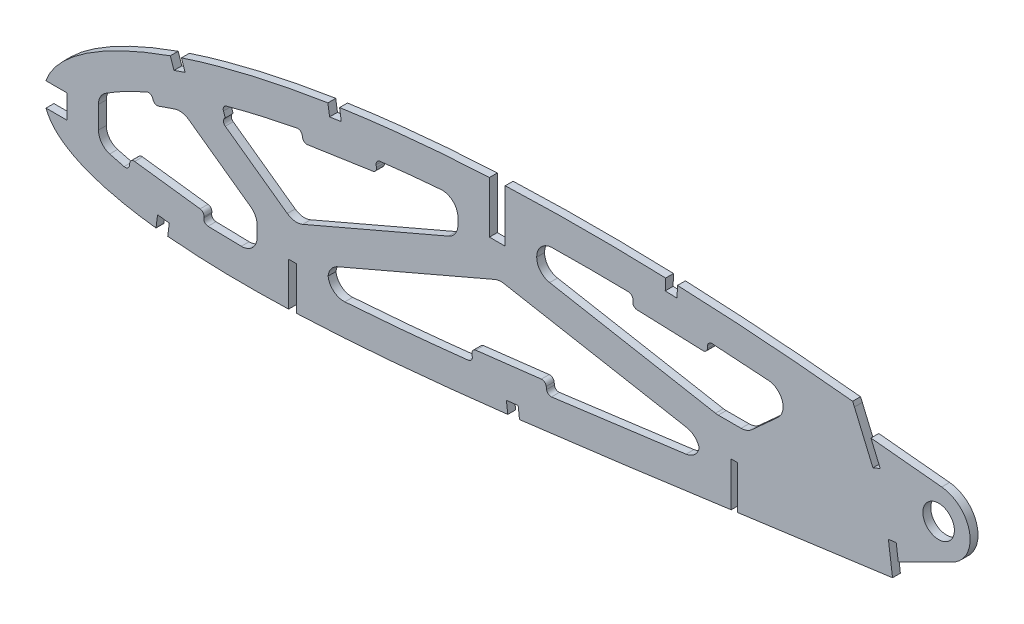
SolidWorks part; units mm, degrees
material "Pine"
ref_plane "Front Plane" through (0, 0, 0) normal (0, 0, 1) x (1, 0, 0)
ref_plane "Top Plane" through (0, 0, 0) normal (0, 1, 0) x (1, 0, 0)
ref_plane "Right Plane" through (0, 0, 0) normal (1, 0, 0) x (0, 0, -1)
curve "Curve2"
  spline degree 3 poles (520.229, 0.8111, 0) (520.1892, 0.8357, 0) (520.0299, 0.9341, 0) (519.6711, 1.1542, 0) (519.0735, 1.5208, 0) (518.237, 2.0313, 0) (517.1622, 2.6844, 0) (515.8486, 3.4756, 0) (514.2969, 4.4021, 0) (512.5075, 5.4598, 0) (510.4807, 6.6436, 0) (508.2172, 7.9486, 0) (505.7172, 9.3676, 0) (502.9816, 10.8948, 0) (500.0114, 12.5227, 0) (496.8072, 14.2443, 0) (493.3701, 16.0505, 0) (489.7015, 17.9338, 0) (485.8019, 19.8836, 0) (481.6733, 21.8919, 0) (477.317, 23.9487, 0) (472.7345, 26.0429, 0) (467.9284, 28.1661, 0) (462.9001, 30.305, 0) (457.6524, 32.4505, 0) (452.1876, 34.5902, 0) (446.5089, 36.7144, 0) (440.6184, 38.8094, 0) (434.5207, 40.866, 0) (428.2186, 42.8708, 0) (421.7166, 44.813, 0) (415.0186, 46.68, 0) (408.1302, 48.4622, 0) (401.0555, 50.1466, 0) (393.8008, 51.7219, 0) (386.3718, 53.1787, 0) (378.7746, 54.5024, 0) (371.0303, 55.692, 0) (363.2636, 56.6815, 0) (355.5128, 57.652, 0) (347.7736, 58.5637, 0) (339.9398, 59.4368, 0) (332.019, 60.2663, 0) (324.019, 61.0497, 0) (315.9478, 61.7836, 0) (307.814, 62.4658, 0) (299.6253, 63.0925, 0) (291.3904, 63.6628, 0) (283.1174, 64.1714, 0) (274.8152, 64.6183, 0) (266.4922, 65.0001, 0) (258.157, 65.3142, 0) (249.8185, 65.5589, 0) (241.4854, 65.7316, 0) (233.1666, 65.8314, 0) (224.8708, 65.8555, 0) (216.6071, 65.8035, 0) (208.384, 65.6736, 0) (200.2107, 65.464, 0) (192.0958, 65.1743, 0) (184.048, 64.8046, 0) (176.0762, 64.3519, 0) (168.189, 63.8191, 0) (160.3952, 63.2038, 0) (152.7034, 62.506, 0) (145.1216, 61.7286, 0) (137.6583, 60.8693, 0) (130.3214, 59.9308, 0) (123.1191, 58.9147, 0) (116.0593, 57.8206, 0) (109.1496, 56.6517, 0) (102.3976, 55.409, 0) (95.8102, 54.0963, 0) (89.3948, 52.714, 0) (83.1581, 51.266, 0) (77.1065, 49.7551, 0) (71.2467, 48.1838, 0) (65.5845, 46.5561, 0) (60.1256, 44.8756, 0) (54.8764, 43.1442, 0) (49.8409, 41.3683, 0) (45.0253, 39.5493, 0) (40.4333, 37.6928, 0) (36.0702, 35.8014, 0) (31.9393, 33.8806, 0) (28.0452, 31.9329, 0) (24.3908, 29.9636, 0) (20.9797, 27.9757, 0) (17.8153, 25.973, 0) (14.8987, 23.9604, 0) (12.2341, 21.9394, 0) (9.8224, 19.9149, 0) (7.6651, 17.8901, 0) (5.7652, 15.8664, 0) (4.1228, 13.8473, 0) (2.7399, 11.8344, 0) (1.6168, 9.8297, 0) (0.7561, 7.8345, 0) (0.1568, 5.85, 0) (-0.1712, 3.8792, 0) (-0.2528, 1.9205, 0) (-0.0842, 0.6392, 0) (0, 0, 0) knots 0 0 0 0 0.000254 0.001015 0.002283 0.004057 0.006331 0.009105 0.012374 0.016134 0.02038 0.025106 0.030306 0.035972 0.0421 0.048678 0.055702 0.06316 0.071046 0.07935 0.088063 0.097176 0.106678 0.116562 0.126814 0.137428 0.148394 0.1597 0.171338 0.183298 0.19557 0.208144 0.221012 0.234162 0.247587 0.261277 0.275223 0.289414 0.303771 0.317689 0.331784 0.34604 0.360444 0.374983 0.38964 0.404403 0.419257 0.434187 0.449177 0.464215 0.479284 0.49437 0.509458 0.524532 0.539579 0.554583 0.56953 0.584403 0.599191 0.613877 0.628447 0.642889 0.657186 0.671326 0.685294 0.699078 0.712665 0.726043 0.739198 0.752118 0.764792 0.777208 0.789356 0.801224 0.812804 0.824083 0.835055 0.84571 0.856038 0.866034 0.875689 0.884998 0.893953 0.902553 0.910789 0.918661 0.926166 0.933303 0.940071 0.946475 0.952518 0.958205 0.963547 0.968557 0.97325 0.977651 0.981787 0.985694 0.989415 0.993001 0.996508 1 1 1 1
curve "Curve3"
  spline degree 3 poles (0, 0, 0) (0.1336, -0.6306, 0) (0.4014, -1.8948, 0) (1.129, -3.7148, 0) (2.0912, -5.4642, 0) (3.3081, -7.1386, 0) (4.7718, -8.7374, 0) (6.479, -10.2623, 0) (8.428, -11.7125, 0) (10.6162, -13.0874, 0) (13.0406, -14.3883, 0) (15.6982, -15.6145, 0) (18.5868, -16.7656, 0) (21.7032, -17.8401, 0) (25.0435, -18.8396, 0) (28.6046, -19.7616, 0) (32.3825, -20.6074, 0) (36.3735, -21.375, 0) (40.5732, -22.065, 0) (44.9774, -22.6771, 0) (49.5814, -23.2117, 0) (54.3808, -23.6676, 0) (59.3708, -24.0458, 0) (64.5464, -24.3466, 0) (69.9027, -24.5709, 0) (75.4344, -24.718, 0) (81.1363, -24.7899, 0) (87.003, -24.788, 0) (93.0289, -24.7115, 0) (99.2088, -24.5648, 0) (105.5368, -24.3469, 0) (112.0073, -24.0604, 0) (118.6142, -23.7083, 0) (125.3518, -23.2917, 0) (132.2141, -22.8125, 0) (139.1951, -22.2745, 0) (146.2885, -21.679, 0) (153.4882, -21.0296, 0) (160.7876, -20.3295, 0) (168.1806, -19.5808, 0) (175.6606, -18.7872, 0) (183.2209, -17.9512, 0) (190.8551, -17.0772, 0) (198.5563, -16.1668, 0) (206.3179, -15.2253, 0) (214.1326, -14.2544, 0) (221.9939, -13.2579, 0) (229.8947, -12.2404, 0) (237.8276, -11.2019, 0) (245.786, -10.1497, 0) (253.7621, -9.0829, 0) (261.7491, -8.0072, 0) (269.7395, -6.9257, 0) (277.7256, -5.8389, 0) (285.7003, -4.7513, 0) (293.6562, -3.6657, 0) (301.5856, -2.5824, 0) (309.4812, -1.5067, 0) (317.3352, -0.4385, 0) (325.1402, 0.6201, 0) (332.8888, 1.6659, 0) (340.5737, 2.6975, 0) (348.187, 3.7144, 0) (355.721, 4.7168, 0) (363.0553, 5.6745, 0) (370.1707, 6.6383, 0) (377.0913, 7.4284, 0) (383.9258, 8.1028, 0) (390.6811, 8.6557, 0) (397.3493, 9.0951, 0) (403.9227, 9.4241, 0) (410.3934, 9.6473, 0) (416.7532, 9.7713, 0) (422.9943, 9.7993, 0) (429.1081, 9.7402, 0) (435.0867, 9.5987, 0) (440.9216, 9.3813, 0) (446.6049, 9.0952, 0) (452.1283, 8.7483, 0) (457.4837, 8.3456, 0) (462.6634, 7.8966, 0) (467.6597, 7.4078, 0) (472.4647, 6.8849, 0) (477.0715, 6.3387, 0) (481.4727, 5.7729, 0) (485.6616, 5.1968, 0) (489.6316, 4.6162, 0) (493.3764, 4.0385, 0) (496.89, 3.4693, 0) (500.1667, 2.916, 0) (503.2016, 2.384, 0) (505.9892, 1.8782, 0) (508.5257, 1.4052, 0) (510.8062, 0.9673, 0) (512.8275, 0.5717, 0) (514.5859, 0.2202, 0) (516.0789, -0.0824, 0) (517.3037, -0.3347, 0) (518.2586, -0.5328, 0) (518.9417, -0.6767, 0) (519.3522, -0.7624, 0) (519.5346, -0.8013, 0) (519.5802, -0.8111, 0) knots 0 0 0 0 0.003638 0.007293 0.011028 0.014901 0.018963 0.023258 0.027821 0.032679 0.037853 0.043362 0.049215 0.055422 0.061989 0.068918 0.076211 0.083868 0.091887 0.100266 0.109 0.118085 0.127515 0.137285 0.147388 0.157816 0.168563 0.179619 0.190977 0.202627 0.21456 0.226767 0.239236 0.251959 0.264924 0.27812 0.291536 0.30516 0.318981 0.332985 0.347163 0.361499 0.375981 0.390597 0.405333 0.420175 0.43511 0.450124 0.465203 0.480333 0.495501 0.51069 0.525887 0.541078 0.556247 0.571382 0.586466 0.601485 0.616424 0.631269 0.646007 0.660621 0.675098 0.689423 0.703582 0.716908 0.730009 0.742952 0.755726 0.76832 0.780724 0.792927 0.804916 0.816679 0.828204 0.839475 0.850481 0.861208 0.871639 0.881763 0.891564 0.901027 0.910139 0.918884 0.927249 0.935221 0.942785 0.949928 0.956638 0.962904 0.968712 0.974054 0.978918 0.983297 0.98718 0.990561 0.993433 0.995791 0.99763 0.998946 0.999737 1 1 1 1
sketch "Sketch1" plane through (0, 0, 0) normal (0, 0, 1) x (1, 0, 0)
  line L1 (502.7977, -0.7849) -> (507.4667, -1.7115)
  line L2 (503.4256, 0.7849) -> (507.4667, -1.7115)
  spline S2 degree 3 poles (0, 0) (0.1293, -0.6103) (0.3884, -1.8336) (1.0925, -3.5948) (2.0236, -5.2877) (3.2013, -6.908) (4.6177, -8.4552) (6.2698, -9.9309) (8.1558, -11.3342) (10.2733, -12.6647) (12.6193, -13.9236) (15.1912, -15.1102) (17.9865, -16.2241) (21.0022, -17.2639) (24.2346, -18.231) (27.6807, -19.1233) (31.3366, -19.9418) (35.1986, -20.6846) (39.2627, -21.3523) (43.5246, -21.9446) (47.9799, -22.4619) (52.6243, -22.9031) (57.4531, -23.2691) (62.4616, -23.5602) (67.6448, -23.7773) (72.9979, -23.9196) (78.5156, -23.9892) (84.1928, -23.9873) (90.0241, -23.9133) (96.0044, -23.7713) (102.128, -23.5605) (108.3894, -23.2833) (114.783, -22.9425) (121.303, -22.5394) (127.9436, -22.0756) (134.6991, -21.555) (141.5634, -20.9788) (148.5305, -20.3504) (155.5942, -19.6728) (162.7484, -18.9484) (169.9867, -18.1804) (177.3029, -17.3713) (184.6905, -16.5256) (192.1429, -15.6446) (199.6538, -14.7335) (207.2161, -13.794) (214.8235, -12.8296) (222.4691, -11.845) (230.1458, -10.84) (237.8471, -9.8218) (245.5656, -8.7896) (253.2946, -7.7486) (261.0269, -6.702) (268.755, -5.6503) (276.4722, -4.5978) (284.1711, -3.5473) (291.8444, -2.499) (299.485, -1.458) (307.0852, -0.4243) (314.6382, 0.6001) (322.1365, 1.6121) (329.5732, 2.6104) (336.9406, 3.5944) (344.2312, 4.5645) (351.3286, 5.4912) (358.2142, 6.4239) (364.9113, 7.1885) (371.525, 7.8411) (378.0621, 8.3761) (384.5149, 8.8013) (390.876, 9.1197) (397.1377, 9.3357) (403.2921, 9.4557) (409.3316, 9.4828) (415.2479, 9.4256) (421.0334, 9.2887) (426.6799, 9.0783) (432.1795, 8.8014) (437.5246, 8.4657) (442.7069, 8.076) (447.7194, 7.6415) (452.5543, 7.1686) (457.2041, 6.6625) (461.6621, 6.134) (465.9211, 5.5865) (469.9748, 5.029) (473.8165, 4.4671) (477.4403, 3.9081) (480.8404, 3.3572) (484.0114, 2.8219) (486.9482, 2.3069) (489.6458, 1.8176) (492.1004, 1.3598) (494.3072, 0.9361) (496.2632, 0.5532) (497.9648, 0.2131) (499.4095, -0.0797) (500.5948, -0.3239) (501.5189, -0.5155) (502.1799, -0.6549) (502.5771, -0.7378) (502.7536, -0.7754) (502.7977, -0.7849) knots 0 0 0 0 0.003638 0.007293 0.011028 0.014901 0.018963 0.023258 0.027821 0.032679 0.037853 0.043362 0.049215 0.055422 0.061989 0.068918 0.076211 0.083868 0.091887 0.100266 0.109 0.118085 0.127515 0.137285 0.147388 0.157816 0.168563 0.179619 0.190977 0.202627 0.21456 0.226767 0.239236 0.251959 0.264924 0.27812 0.291536 0.30516 0.318981 0.332985 0.347163 0.361499 0.375981 0.390597 0.405333 0.420175 0.43511 0.450124 0.465203 0.480333 0.495501 0.51069 0.525887 0.541078 0.556247 0.571382 0.586466 0.601485 0.616424 0.631269 0.646007 0.660621 0.675098 0.689423 0.703582 0.716908 0.730009 0.742952 0.755726 0.76832 0.780724 0.792927 0.804916 0.816679 0.828204 0.839475 0.850481 0.861208 0.871639 0.881763 0.891564 0.901027 0.910139 0.918884 0.927249 0.935221 0.942785 0.949928 0.956638 0.962904 0.968712 0.974054 0.978918 0.983297 0.98718 0.990561 0.993433 0.995791 0.99763 0.998946 0.999737 1 1 1 1
  spline S3 degree 3 poles (503.4256, 0.7849) (503.3871, 0.8087) (503.2329, 0.9039) (502.8857, 1.1169) (502.3075, 1.4716) (501.498, 1.9657) (500.4579, 2.5977) (499.1867, 3.3633) (497.6851, 4.26) (495.9535, 5.2834) (493.9922, 6.429) (491.8018, 7.6919) (489.3825, 9.0651) (486.7353, 10.5429) (483.8611, 12.1183) (480.7604, 13.7842) (477.4343, 15.5321) (473.8841, 17.3545) (470.1105, 19.2413) (466.1153, 21.1848) (461.8997, 23.1751) (457.4652, 25.2017) (452.8143, 27.2563) (447.9484, 29.3262) (442.8702, 31.4023) (437.5819, 33.4729) (432.0866, 35.5285) (426.3865, 37.5558) (420.4857, 39.546) (414.3871, 41.4861) (408.0952, 43.3656) (401.6135, 45.1723) (394.9475, 46.8969) (388.1015, 48.5268) (381.0811, 50.0513) (373.8919, 51.461) (366.5401, 52.742) (359.046, 53.8931) (351.5302, 54.8507) (344.0298, 55.7898) (336.5405, 56.6721) (328.9598, 57.517) (321.2948, 58.3197) (313.5531, 59.0778) (305.7427, 59.788) (297.8716, 60.4482) (289.9474, 61.0547) (281.9785, 61.6064) (273.9728, 62.0987) (265.9387, 62.5311) (257.8845, 62.9006) (249.8186, 63.2046) (241.7494, 63.4413) (233.6854, 63.6085) (225.6353, 63.7051) (217.6075, 63.7284) (209.6107, 63.678) (201.6532, 63.5523) (193.7439, 63.3495) (185.8911, 63.0691) (178.1033, 62.7114) (170.3889, 62.2734) (162.7565, 61.7577) (155.2145, 61.1624) (147.7711, 60.4871) (140.4342, 59.7347) (133.2119, 58.9033) (126.1121, 57.995) (119.1423, 57.0118) (112.3106, 55.953) (105.6241, 54.8218) (99.0901, 53.6193) (92.7156, 52.349) (86.5074, 51.0113) (80.4721, 49.6101) (74.616, 48.148) (68.9454, 46.6275) (63.4661, 45.0524) (58.1835, 43.4261) (53.1039, 41.7506) (48.2311, 40.0321) (43.571, 38.2719) (39.1273, 36.4754) (34.9051, 34.645) (30.9076, 32.7863) (27.1393, 30.9015) (23.603, 28.9958) (20.3021, 27.0721) (17.2398, 25.134) (14.4175, 23.1865) (11.839, 21.2308) (9.5051, 19.2717) (7.4175, 17.3123) (5.579, 15.3539) (3.9896, 13.4) (2.6514, 11.4522) (1.5646, 9.5122) (0.7317, 7.5814) (0.1518, 5.6611) (-0.1657, 3.7539) (-0.2447, 1.8584) (-0.0814, 0.6186) (0, 0) knots 0 0 0 0 0.000254 0.001015 0.002283 0.004057 0.006331 0.009105 0.012374 0.016134 0.02038 0.025106 0.030306 0.035972 0.0421 0.048678 0.055702 0.06316 0.071046 0.07935 0.088063 0.097176 0.106678 0.116562 0.126814 0.137428 0.148394 0.1597 0.171338 0.183298 0.19557 0.208144 0.221012 0.234162 0.247587 0.261277 0.275223 0.289414 0.303771 0.317689 0.331784 0.34604 0.360444 0.374983 0.38964 0.404403 0.419257 0.434187 0.449177 0.464215 0.479284 0.49437 0.509458 0.524532 0.539579 0.554583 0.56953 0.584403 0.599191 0.613877 0.628447 0.642889 0.657186 0.671326 0.685294 0.699078 0.712665 0.726043 0.739198 0.752118 0.764792 0.777208 0.789356 0.801224 0.812804 0.824083 0.835055 0.84571 0.856038 0.866034 0.875689 0.884998 0.893953 0.902553 0.910789 0.918661 0.926166 0.933303 0.940071 0.946475 0.952518 0.958205 0.963547 0.968557 0.97325 0.977651 0.981787 0.985694 0.989415 0.993001 0.996508 1 1 1 1
extrude "Boss-Extrude1" add sketch "Sketch1" along normal blind 3.175
sketch "Sketch2" plane through (0, 0, 0) normal (0, 0, -1) x (-1, 0, 0)
  line L2 (-279.413, 13.2185) -> (-279.413, -4.2647)
  line L7 (-185.7505, 63.1075) -> (-185.7505, 41.9342)
  line L10 (-101.613, -6.2566) -> (-101.613, -23.2656)
  line L14 (-276.873, 13.2185) -> (-276.873, -4.2647)
  line L19 (-179.4005, 63.1075) -> (-179.4005, 41.9342)
  line L22 (-98.438, -6.2566) -> (-98.438, -23.2656)
  line L24 (-279.413, -4.2647) -> (-279.413, -6.8186)
  line L25 (-279.413, -6.8186) -> (-276.873, -5.1225)
  line L26 (-276.873, -5.1225) -> (-276.873, -4.2647)
  line L27 (-279.413, 13.2185) -> (-276.873, 13.2185)
  line L28 (-185.7505, 41.9342) -> (-179.4005, 41.9342)
  line L29 (-185.7505, 63.1075) -> (-185.7505, 65.7574)
  line L30 (-185.7505, 65.7574) -> (-179.4005, 64.4325)
  line L31 (-179.4005, 64.4325) -> (-179.4005, 63.1075)
  line L32 (-101.613, -6.2566) -> (-98.438, -6.2566)
  line L33 (-101.613, -23.2656) -> (-101.613, -26.5147)
  line L34 (-101.613, -26.5147) -> (-98.438, -24.3947)
  line L35 (-98.438, -24.3947) -> (-98.438, -23.2656)
extrude "Cut-Extrude1" cut sketch "Sketch2" against normal blind 7.62
sketch "Sketch4" plane through (0, 0, 3.175) normal (0, 0, 1) x (1, 0, 0)
  circle A1 centre (360.4876, 33.2326) radius 6.35
extrude "Cut-Extrude2" cut sketch "Sketch4" against normal blind 7.62
sketch "Sketch5" plane through (0, 0, 3.175) normal (0, 0, 1) x (1, 0, 0)
  line L0 (344.0371, 55.7798) -> (341.5766, 35.5304) construction
  line L1 (341.6021, 30.734) -> (344.2177, 10.9645) construction
  line L2 (344.0371, 55.7798) -> (385.7291, 50.7139) construction
  line L3 (345.0505, 4.6694) -> (385.9109, 10.0752) construction
  line L4 (360.4876, 33.2326) -> (341.5766, 35.5304) construction
  line L5 (360.4876, 33.2326) -> (342.9613, 25.7671) construction
  line L6 (342.9613, 25.7671) -> (333.1968, 48.6907) construction
  line L7 (333.1968, 48.6907) -> (336.9295, 39.9276)
  line L9 (336.9295, 39.9276) -> (334.0085, 38.6833)
  line L10 (326.543, 56.2096) -> (334.0085, 38.6833)
  line L11 (344.2177, 10.9645) -> (343.3848, 17.2597)
  line L13 (343.3848, 17.2597) -> (340.2372, 16.8432)
  line L14 (341.9029, 4.2529) -> (340.2372, 16.8432)
  line L15 (344.2177, 10.9645) -> (366.1398, 21.8597)
  line L16 (333.1968, 48.6907) -> (361.7362, 45.871)
  line L17 (326.543, 56.2096) -> (324.1984, 61.4585)
  line L18 (324.1984, 61.4585) -> (523.3056, 35.5304)
  line L19 (523.3056, 35.5304) -> (514.4062, -32.8098)
  line L20 (514.4062, -32.8098) -> (341.9029, 3.5538)
  line L21 (341.9029, 3.5538) -> (341.9029, 4.2529)
  circle A2 centre (360.4876, 33.2326) radius 19.05
  circle A3 centre (360.4876, 33.2326) radius 19.05 construction
  circle A5 centre (360.4876, 33.2326) radius 12.7
  arc A6 (366.1398, 21.8597) -> (361.7362, 45.871) centre (360.4876, 33.2326) ccw
  spline S0 degree 3 poles (503.4256, 0.7849) (503.3871, 0.8087) (503.2329, 0.9039) (502.8857, 1.1169) (502.3075, 1.4716) (501.498, 1.9657) (500.4579, 2.5977) (499.1867, 3.3633) (497.6851, 4.26) (495.9535, 5.2834) (493.9922, 6.429) (491.8018, 7.6919) (489.3825, 9.0651) (486.7353, 10.5429) (483.8611, 12.1183) (480.7604, 13.7842) (477.4343, 15.5321) (473.8841, 17.3545) (470.1105, 19.2413) (466.1153, 21.1848) (461.8997, 23.1751) (457.4652, 25.2017) (452.8143, 27.2563) (447.9484, 29.3262) (442.8702, 31.4023) (437.5819, 33.4729) (432.0866, 35.5285) (426.3865, 37.5558) (420.4857, 39.546) (414.3871, 41.4861) (408.0952, 43.3656) (401.6135, 45.1723) (394.9475, 46.8969) (388.1015, 48.5268) (381.0811, 50.0513) (373.8919, 51.461) (366.5401, 52.742) (359.046, 53.8931) (351.5302, 54.8507) (344.0298, 55.7898) (336.5405, 56.6721) (328.9598, 57.517) (321.2948, 58.3197) (313.5531, 59.0778) (305.7427, 59.788) (297.8716, 60.4482) (289.9474, 61.0547) (281.9785, 61.6064) (273.9728, 62.0987) (265.9387, 62.5311) (257.8845, 62.9006) (249.8186, 63.2046) (241.7494, 63.4413) (233.6854, 63.6085) (225.6353, 63.7051) (217.6075, 63.7284) (209.6107, 63.678) (201.6532, 63.5523) (193.7439, 63.3495) (188.4487, 63.1604) (185.7907, 63.0517) (185.7505, 63.0501) knots 0 0 0 0 0.000254 0.001015 0.002283 0.004057 0.006331 0.009105 0.012374 0.016134 0.02038 0.025106 0.030306 0.035972 0.0421 0.048678 0.055702 0.06316 0.071046 0.07935 0.088063 0.097176 0.106678 0.116562 0.126814 0.137428 0.148394 0.1597 0.171338 0.183298 0.19557 0.208144 0.221012 0.234162 0.247587 0.261277 0.275223 0.289414 0.303771 0.317689 0.331784 0.34604 0.360444 0.374983 0.38964 0.404403 0.419257 0.434187 0.449177 0.464215 0.479284 0.49437 0.509458 0.524532 0.539579 0.554583 0.56953 0.584403 0.599191 0.613877 0.614102 0.614102 0.614102 0.614102 construction
  spline S1 degree 3 poles (279.413, -4.1965) (281.0019, -3.9797) (285.1494, -3.4137) (291.8444, -2.499) (299.485, -1.458) (307.0852, -0.4243) (314.6382, 0.6001) (322.1365, 1.6121) (329.5732, 2.6104) (336.9406, 3.5944) (344.2312, 4.5645) (351.3286, 5.4912) (358.2142, 6.4239) (364.9113, 7.1885) (371.525, 7.8411) (378.0621, 8.3761) (384.5149, 8.8013) (390.876, 9.1197) (397.1377, 9.3357) (403.2921, 9.4557) (409.3316, 9.4828) (415.2479, 9.4256) (421.0334, 9.2887) (426.6799, 9.0783) (432.1795, 8.8014) (437.5246, 8.4657) (442.7069, 8.076) (447.7194, 7.6415) (452.5543, 7.1686) (457.2041, 6.6625) (461.6621, 6.134) (465.9211, 5.5865) (469.9748, 5.029) (473.8165, 4.4671) (477.4403, 3.9081) (480.8404, 3.3572) (484.0114, 2.8219) (486.9482, 2.3069) (489.6458, 1.8176) (492.1004, 1.3598) (494.3072, 0.9361) (496.2632, 0.5532) (497.9648, 0.2131) (499.4095, -0.0797) (500.5948, -0.3239) (501.5189, -0.5155) (502.1799, -0.6549) (502.5771, -0.7378) (502.7536, -0.7754) (502.7977, -0.7849) knots 0.562015 0.562015 0.562015 0.562015 0.571382 0.586466 0.601485 0.616424 0.631269 0.646007 0.660621 0.675098 0.689423 0.703582 0.716908 0.730009 0.742952 0.755726 0.76832 0.780724 0.792927 0.804916 0.816679 0.828204 0.839475 0.850481 0.861208 0.871639 0.881763 0.891564 0.901027 0.910139 0.918884 0.927249 0.935221 0.942785 0.949928 0.956638 0.962904 0.968712 0.974054 0.978918 0.983297 0.98718 0.990561 0.993433 0.995791 0.99763 0.998946 0.999737 1 1 1 1 construction
  dimension "D2" = 30
  dimension "D3" = 19.05
  dimension "D4" = 3.175
  dimension "D5" = 3.175
  dimension "D6" = 12.7
  dimension "D1" = 12.7
  dimension "D7" = 6.35
extrude "Cut-Extrude3" cut sketch "Sketch5" against normal blind 7.62
sketch "Sketch6" plane through (0, 0, 3.175) normal (0, 0, 1) x (1, 0, 0)
  line L1 (255.026, 58.4269) -> (255.2149, 63.1774)
  line L2 (44.9944, -21.8905) -> (44.8501, -23.0193)
  line L3 (191.5259, -15.7937) -> (190.9681, -11.0621)
  line L4 (49.7085, -22.4931) -> (49.5642, -23.6218)
  line L5 (190.9681, -11.0621) -> (186.2384, -11.6197)
  line L6 (44.8501, -23.0193) -> (49.5642, -23.6218)
  line L7 (119.6665, 52.3947) -> (118.9624, 57.1203)
  line L9 (49.7085, -22.4931) -> (50.3163, -17.7395)
  line L11 (50.3163, -17.7395) -> (45.5978, -17.1393)
  line L13 (56.7196, 38.1139) -> (55.1734, 42.5857)
  line L15 (9.056, -2.3922) -> (9.056, 7.1328)
  line L17 (-0.469, 7.1328) -> (9.056, 7.1328)
  line L19 (186.2384, -11.6197) -> (186.7926, -16.3533)
  line L21 (250.2669, 58.5999) -> (255.026, 58.4269)
  line L23 (250.4318, 63.3556) -> (250.2669, 58.5999)
  line L25 (45.5978, -17.1393) -> (44.9944, -21.8905)
  line L27 (114.956, 51.6928) -> (119.6665, 52.3947)
  line L29 (114.2395, 56.3928) -> (114.956, 51.6928)
  line L31 (-0.469, -2.3922) -> (9.056, -2.3922)
  line L33 (-0.469, -2.3922) -> (-0.469, 7.1328)
  line L35 (50.6672, 41.0436) -> (52.2187, 36.5575)
  line L37 (52.2187, 36.5575) -> (56.7196, 38.1139)
  arc A1 (255.2149, 63.1774) -> (250.4318, 63.3556) centre (144.7927, -2837.1075) ccw
  arc A3 (118.9624, 57.1203) -> (114.2395, 56.3928) centre (328.9064, -1321.5454) ccw
  arc A5 (186.7926, -16.3533) -> (191.5259, -15.7937) centre (-527.8935, 6048.3336) ccw
  spline S1 degree 3 poles (55.1734, 42.5857) (54.4215, 42.3312) (52.9186, 41.8197) (51.4174, 41.3032) (50.6672, 41.0436) knots 0 0 0 0 0.5 1 1 1 1
extrude "Cut-Extrude4" cut sketch "Sketch6" against normal blind 7.62
sketch "Sketch7" plane through (0, 0, 3.175) normal (0, 0, 1) x (1, 0, 0)
  line L38 (285.763, 19.5685) -> (321.4723, 51.9102) construction
  line L39 (56.5444, 31.3343) -> (100.0255, 0.0934) construction
  line L40 (100.0255, 0.0934) -> (182.5755, 35.5842) construction
  line L41 (182.5755, 35.5842) -> (270.523, 19.5685) construction
  line L42 (85.738, 6.4434) -> (107.963, 6.4434) construction
  line L43 (44.3668, 20.4046) -> (43.0161, 24.3103)
  line L44 (21.756, 12.7897) -> (21.756, 12.7897)
  line L45 (21.756, 12.7897) -> (21.756, -4.0456)
  line L46 (34.019, -7.5081) -> (34.5994, -2.938)
  line L47 (34.5994, -2.938) -> (64.5256, -6.7446)
  line L48 (64.5256, -6.7446) -> (63.9935, -10.9062)
  line L49 (85.738, -11.2621) -> (85.738, 2.5398)
  line L50 (114.313, -0.6759) -> (114.313, -10.2393)
  line L51 (55.5107, 24.258) -> (85.738, 2.5398)
  line L52 (55.5107, 24.258) -> (44.3668, 20.4046)
  line L53 (66.8712, 28.1863) -> (44.3668, 20.4046) construction
  line L54 (52.8392, 26.1774) -> (96.3203, -5.0635) construction
  line L55 (85.738, -11.2621) -> (85.738, 6.4434) construction
  line L56 (166.7005, 35.6711) -> (166.7005, 49.2912)
  line L57 (133.4414, 46.121) -> (134.0994, 41.705)
  line L58 (134.0994, 41.705) -> (104.3085, 37.2662)
  line L59 (104.3085, 37.2662) -> (103.6568, 41.5416)
  line L60 (71.5295, 34.1454) -> (72.8724, 30.2615)
  line L61 (72.8724, 30.2615) -> (70.2043, 29.3389)
  line L62 (100.8154, 7.345) -> (180.0674, 41.4179) construction
  line L63 (100.8154, 7.345) -> (166.7005, 35.6711)
  line L64 (55.5107, 24.258) -> (50.368, 22.4797)
  line L65 (72.8724, 30.2615) -> (50.368, 22.4797) construction
  line L66 (70.2043, 29.3389) -> (100.8154, 7.345)
  line L67 (60.2496, 36.4913) -> (100.8154, 7.345) construction
  line L68 (192.1005, 29.2342) -> (166.7005, 29.2342) construction
  line L69 (166.7005, 29.2342) -> (166.7005, 49.2912) construction
  line L70 (172.6885, -5.1029) -> (172.1487, -0.4927)
  line L71 (172.1487, -0.4927) -> (202.094, 3.0374)
  line L72 (202.094, 3.0374) -> (202.6364, -1.5645)
  line L73 (264.173, 6.5433) -> (264.173, 14.2704)
  line L74 (114.313, -0.6759) -> (183.3231, 28.9936)
  line L75 (183.3231, 28.9936) -> (264.173, 14.2704)
  line L76 (261.1195, 51.8512) -> (243.7009, 52.4844)
  line L77 (243.7009, 52.4844) -> (243.8583, 57.0222)
  line L78 (192.1005, 56.9307) -> (192.1005, 35.5842)
  line L79 (192.1005, 35.5842) -> (173.0505, 35.5842)
  line L80 (173.0505, 35.5842) -> (173.0505, 56.0592)
  line L81 (126.2073, 51.5847) -> (126.8829, 47.0498)
  line L82 (126.8829, 47.0498) -> (109.6323, 44.4795)
  line L83 (109.6323, 44.4795) -> (108.9524, 48.9393)
  line L84 (63.3508, 38.3673) -> (64.796, 34.1877)
  line L85 (64.796, 34.1877) -> (48.2928, 28.481)
  line L86 (48.2928, 28.481) -> (46.8317, 32.7058)
  line L87 (12.6276, 13.4828) -> (15.406, 13.4828)
  line L88 (15.406, 13.4828) -> (15.406, -8.1866)
  line L89 (39.4757, -14.9428) -> (40.0986, -10.0387)
  line L90 (40.0986, -10.0387) -> (57.421, -12.2421)
  line L91 (57.421, -12.2421) -> (56.8322, -16.8469)
  line L92 (92.088, -17.5093) -> (92.088, 0.0934)
  line L93 (92.088, 0.0934) -> (107.963, 0.0934)
  line L94 (107.963, 0.0934) -> (107.963, -16.937)
  line L95 (179.7373, -10.6999) -> (179.1935, -6.0562)
  line L96 (179.1935, -6.0562) -> (196.531, -4.0124)
  line L97 (196.531, -4.0124) -> (197.0775, -8.6478)
  line L98 (270.523, 0.9997) -> (270.523, 19.5685)
  line L99 (270.523, 19.5685) -> (285.763, 19.5685)
  line L100 (285.763, 19.5685) -> (285.763, 3.0792)
  line L101 (334.7755, 9.7113) -> (333.1092, 22.3055)
  line L102 (333.1092, 22.3055) -> (348.8471, 24.3877)
  line L103 (348.8471, 24.3877) -> (349.3475, 20.605)
  line L104 (349.3475, 20.605) -> (363.3137, 27.5461)
  line L105 (361.1119, 39.5518) -> (343.2395, 41.3176)
  line L106 (343.2395, 41.3176) -> (345.2601, 36.574)
  line L107 (345.2601, 36.574) -> (330.6549, 30.3527)
  line L108 (330.6549, 30.3527) -> (321.4723, 51.9102)
  line L109 (261.2998, 56.3844) -> (261.1195, 51.8512)
  line L110 (261.1195, 51.8512) -> (243.7009, 52.4844) construction
  line L111 (243.7009, 52.4844) -> (243.8583, 57.0222) construction
  line L112 (192.1005, 56.9307) -> (192.1005, 35.5842) construction
  line L113 (192.1005, 35.5842) -> (173.0505, 35.5842) construction
  line L114 (173.0505, 35.5842) -> (173.0505, 56.0592) construction
  line L115 (126.2073, 51.5847) -> (126.8829, 47.0498) construction
  line L116 (126.8829, 47.0498) -> (109.6323, 44.4795) construction
  line L117 (109.6323, 44.4795) -> (108.9524, 48.9393) construction
  line L118 (63.3508, 38.3673) -> (64.796, 34.1877) construction
  line L119 (64.796, 34.1877) -> (48.2928, 28.481) construction
  line L120 (48.2928, 28.481) -> (46.8317, 32.7058) construction
  line L121 (12.6276, 13.4828) -> (15.406, 13.4828) construction
  line L122 (15.406, 13.4828) -> (15.406, -8.1866) construction
  line L123 (39.4757, -14.9428) -> (40.0986, -10.0387) construction
  line L124 (40.0986, -10.0387) -> (57.421, -12.2421) construction
  line L125 (57.421, -12.2421) -> (56.8322, -16.8469) construction
  line L126 (92.088, -17.5093) -> (92.088, 0.0934) construction
  line L127 (92.088, 0.0934) -> (107.963, 0.0934) construction
  line L128 (107.963, 0.0934) -> (107.963, -16.937) construction
  line L129 (179.7373, -10.6999) -> (179.1935, -6.0562) construction
  line L130 (179.1935, -6.0562) -> (196.531, -4.0124) construction
  line L131 (196.531, -4.0124) -> (197.0775, -8.6478) construction
  line L132 (270.523, 0.9997) -> (270.523, 19.5685) construction
  line L133 (270.523, 19.5685) -> (285.763, 19.5685) construction
  line L143 (261.2998, 56.3844) -> (261.1195, 51.8512) construction
  line L144 (102.5336, -5.7403) -> (183.3231, 28.9936) construction
  line L145 (114.313, 0.0934) -> (114.313, -10.2393) construction
  line L146 (183.3231, 28.9936) -> (269.3853, 13.3212) construction
  line L147 (264.173, 6.5433) -> (264.173, 19.5685) construction
  line L148 (198.4505, 39.1477) -> (271.0965, 25.9185)
  line L149 (271.0965, 25.9185) -> (283.3148, 25.9185)
  line L150 (283.3148, 25.9185) -> (306.5461, 46.9589)
  line L151 (267.3902, 49.7303) -> (267.213, 45.2755)
  line L152 (267.213, 45.2755) -> (237.1349, 46.3689)
  line L153 (237.1349, 46.3689) -> (237.2896, 50.8282)
  line L154 (198.4505, 50.7625) -> (198.4505, 39.1477)
  line L155 (183.7132, 41.8315) -> (271.0965, 25.9185) construction
  line L156 (198.4505, 50.7625) -> (198.4505, 35.5842) construction
  arc A2 (363.3137, 27.5461) -> (361.1119, 39.5518) centre (360.4876, 33.2326) ccw
  spline S10 degree 1 poles (43.0161, 24.3103) (21.756, 12.7897) knots 0 0 1 1 construction
  spline S11 degree 1 poles (21.756, -4.0456) (34.019, -7.5081) knots 0 0 1 1 construction
  spline S12 degree 1 poles (63.9935, -10.9062) (85.738, -11.2621) knots 0 0 1 1 construction
  spline S13 degree 3 poles (43.0161, 24.3103) (41.1229, 23.5034) (37.3558, 21.8183) (31.8701, 19.076) (27.4854, 16.5936) (24.139, 14.4651) (22.5442, 13.3628) (21.756, 12.7897) knots 0.172231 0.172231 0.172231 0.172231 0.334908 0.497586 0.660263 0.741602 0.82294 0.82294 0.82294 0.82294
  spline S14 degree 3 poles (21.756, -4.0456) (22.7224, -4.4194) (24.6639, -5.1031) (27.7075, -6.0145) (30.8257, -6.8154) (32.9554, -7.2879) (34.019, -7.5081) knots 0.175886 0.175886 0.175886 0.175886 0.313722 0.451559 0.589396 0.727233 0.727233 0.727233 0.727233
  spline S15 degree 3 poles (63.9935, -10.9062) (65.7989, -10.9911) (69.4079, -11.1285) (74.8436, -11.2498) (80.2854, -11.2958) (83.9212, -11.2803) (85.738, -11.2621) knots 0.194871 0.194871 0.194871 0.194871 0.351594 0.508318 0.665041 0.821764 0.821764 0.821764 0.821764
  spline S16 degree 1 poles (166.7005, 49.2912) (133.4414, 46.121) knots 0 0 1 1 construction
  spline S17 degree 1 poles (103.6568, 41.5416) (71.5295, 34.1454) knots 0 0 1 1 construction
  spline S18 degree 3 poles (166.7005, 49.2912) (163.9203, 49.1002) (158.3611, 48.6839) (150.0379, 47.9515) (141.729, 47.1059) (136.2026, 46.4631) (133.4414, 46.121) knots 0.144446 0.144446 0.144446 0.144446 0.32377 0.503095 0.68242 0.861745 0.861745 0.861745 0.861745
  spline S19 degree 3 poles (103.6568, 41.5416) (100.9493, 41.0371) (95.5412, 39.9765) (87.4786, 38.2239) (79.4635, 36.2962) (74.1688, 34.8862) (71.5295, 34.1454) knots 0.14006 0.14006 0.14006 0.14006 0.319105 0.49815 0.677195 0.85624 0.85624 0.85624 0.85624
  spline S20 degree 3 poles (836.7345, 2530.2651) (1494.1354, -648.7435) (855.5072, 58.1796) (-203.1926, 56.8296) (-624.0643, -251.2468) (-584.0737, -2702.6011) knots -36.44766 -36.44766 -36.44766 -36.44766 0.5 0.5 24.90877 24.90877 24.90877 24.90877 only from (243.8583, 57.0222) to (192.1005, 56.9307)
  spline S21 degree 3 poles (209.5523, 2861.3643) (1837.0728, -2856.6416) (-1003.4797, 2993.4318) (-169.6675, -2835.0454) knots -29.379997 -29.379997 -29.379997 -29.379997 23.193916 23.193916 23.193916 23.193916 only from (173.0505, 56.0592) to (126.2073, 51.5847)
  spline S22 degree 3 poles (-451.6208, 2897.9458) (886.2414, -277.7827) (431.2531, 123.4775) (82.1806, 43.4935) (78.3883, 42.5631) (-143.2227, -15.9667) (-300.1066, -293.2518) (195.4395, -2922.7092) knots -22.187419 -22.187419 -22.187419 -22.187419 0.5 0.5 0.75 0.75 15.180652 15.180652 15.180652 15.180652 only from (108.9524, 48.9393) to (63.3508, 38.3673)
  spline S23 degree 3 poles (-635.4444, 2917.247) (517.9146, -112.2314) (211.1964, 106.5507) (34.7104, 27.5798) (31.7463, 26.1477) (25.9311, 23.0455) (23.0975, 21.3861) (19.013, 18.654) (17.6796, 17.7022) (-38.9194, -26.3142) (-26.9994, -167.7253) (1529.5428, -2570.153) knots -14.195107 -14.195107 -14.195107 -14.195107 0.25 0.25 0.5 0.5 0.75 0.75 0.875 0.875 6.211528 6.211528 6.211528 6.211528 only from (46.8317, 32.7058) to (12.6276, 13.4828)
  spline S24 degree 3 poles (2858.0831, 935.4252) (-71.4955, 134.6855) (-35.3837, 12.7565) (19.2464, -9.8941) (20.224, -10.2646) (23.1781, -11.3032) (25.175, -11.9) (29.2068, -12.9617) (31.2418, -13.4263) (165.1647, -40.5078) (361.246, 141.243) (-2151.995, -2059.4075) knots -6.799313 -6.799313 -6.799313 -6.799313 0.125 0.125 0.25 0.25 0.5 0.5 0.75 0.75 16.836448 16.836448 16.836448 16.836448 only from (15.406, -8.1866) to (39.4757, -14.9428)
  spline S25 degree 3 poles (-75.914, 2946.7805) (-331.1622, 144.1971) (-128.6258, -14.3049) (348.2461, -22) (622.5929, 258.0744) (890.3689, -2834.7958) knots -16.774716 -16.774716 -16.774716 -16.774716 0.5 0.5 23.789866 23.789866 23.789866 23.789866 only from (56.8322, -16.8469) to (92.088, -17.5093)
  spline S26 degree 3 poles (-970.2713, 2709.0335) (-497.9352, 98.9539) (-181.0049, -37.8755) (131.933, -15.4162) (137.9182, -14.9266) (562.6495, 23.1507) (960.5365, 285.3011) (1542.6041, -2503.8733) knots -12.562186 -12.562186 -12.562186 -12.562186 0.25 0.25 0.5 0.5 18.004046 18.004046 18.004046 18.004046 only from (107.963, -16.937) to (179.7373, -10.6999)
  spline S27 degree 3 poles (-1403.1433, 2357.082) (-662.3764, -72.651) (-210.9958, -62.8251) (749.3812, 64.2921) (1255.3001, 205.0713) (2086.4255, -2130.102) knots -17.671294 -17.671294 -17.671294 -17.671294 0.5 0.5 21.561637 21.561637 21.561637 21.561637 only from (197.0775, -8.6478) to (270.523, 0.9997)
  spline S28 degree 3 poles (-711.614, 75.459) (-351.4279, -92.8313) (-21.2155, -38.5255) (648.896, 52.3247) (989.5664, 83.1656) (1329.8312, 109.0121) knots -19.790359 -19.790359 -19.790359 -19.790359 0.5 0.5 21.227857 21.227857 21.227857 21.227857 only from (285.763, 3.0792) to (334.7755, 9.7113)
  spline S29 degree 3 poles (1131.2784, 1945.055) (2245.2956, -2867.3399) (-537.8914, 2983.102) (-978.4714, -2461.7639) knots -38.564369 -38.564369 -38.564369 -38.564369 26.988277 26.988277 26.988277 26.988277 only from (321.4723, 51.9102) to (261.2998, 56.3844)
  spline S30 degree 3 poles (243.8583, 57.0222) (235.2336, 57.259) (226.606, 57.3776) (209.3511, 57.3556) (200.7237, 57.2156) (192.1005, 56.9307) knots 0 0 0 0 0.5 0.5 1 1 1 1 construction
  spline S31 degree 3 poles (173.0505, 56.0592) (157.3877, 55.1358) (141.7546, 53.6976) (126.2073, 51.5847) knots 0 0 0 0 1 1 1 1 construction
  spline S32 degree 3 poles (108.9524, 48.9393) (101.2569, 47.619) (93.5944, 46.1088) (82.1806, 43.4935) (78.3883, 42.5631) (70.8406, 40.5697) (67.085, 39.507) (63.3508, 38.3673) knots 0 0 0 0 0.5 0.5 0.75 0.75 1 1 1 1 construction
  spline S33 degree 3 poles (46.8317, 32.7058) (43.7577, 31.5215) (40.7153, 30.2667) (34.7104, 27.5798) (31.7463, 26.1477) (25.9311, 23.0455) (23.0975, 21.3861) (19.013, 18.654) (17.6796, 17.7022) (15.0888, 15.6874) (13.8303, 14.626) (12.6276, 13.4828) knots 0 0 0 0 0.25 0.25 0.5 0.5 0.75 0.75 0.875 0.875 1 1 1 1 construction
  spline S34 degree 3 poles (15.406, -8.1866) (16.3459, -8.6567) (17.3089, -9.0908) (19.2464, -9.8941) (20.224, -10.2646) (23.1781, -11.3032) (25.175, -11.9) (29.2068, -12.9617) (31.2418, -13.4263) (35.3407, -14.2552) (37.4057, -14.6193) (39.4757, -14.9428) knots 0 0 0 0 0.125 0.125 0.25 0.25 0.5 0.5 0.75 0.75 1 1 1 1 construction
  spline S35 degree 3 poles (56.8322, -16.8469) (62.6981, -17.2621) (68.5756, -17.487) (80.3314, -17.6767) (86.2096, -17.6405) (92.088, -17.5093) knots 0 0 0 0 0.5 0.5 1 1 1 1 construction
  spline S36 degree 3 poles (107.963, -16.937) (113.9611, -16.6453) (119.9543, -16.2759) (131.933, -15.4162) (137.9182, -14.9266) (155.8605, -13.3181) (167.805, -12.0625) (179.7373, -10.6999) knots 0 0 0 0 0.25 0.25 0.5 0.5 1 1 1 1 construction
  spline S37 degree 3 poles (197.0775, -8.6478) (209.3327, -7.1519) (221.5771, -5.569) (246.056, -2.3289) (258.29, -0.668) (270.523, 0.9997) knots 0 0 0 0 0.5 0.5 1 1 1 1 construction
  spline S38 degree 1 poles (114.313, -10.2393) (172.6885, -5.1029) knots 0 0 1 1 construction
  spline S39 degree 3 poles (321.4723, 51.9102) (301.4601, 53.9524) (281.3952, 55.4698) (261.2998, 56.3844) knots 0 0 0 0 1 1 1 1 construction
  spline S40 degree 1 poles (202.6364, -1.5645) (264.173, 6.5433) knots 0 0 1 1 construction
  spline S41 degree 3 poles (114.313, -10.2393) (119.1794, -9.9573) (128.9011, -9.2992) (143.4997, -8.0817) (158.0937, -6.6789) (167.8262, -5.6415) (172.6885, -5.1029) knots 0.093353 0.093353 0.093353 0.093353 0.297846 0.50234 0.706833 0.911326 0.911326 0.911326 0.911326
  spline S42 degree 3 poles (202.6364, -1.5645) (207.7655, -0.9263) (218.0177, 0.3774) (233.4029, 2.3948) (248.7855, 4.4534) (259.0446, 5.8454) (264.173, 6.5433) knots 0.086276 0.086276 0.086276 0.086276 0.295995 0.505715 0.715434 0.925153 0.925153 0.925153 0.925153
  spline S43 degree 1 poles (306.5461, 46.9589) (267.3902, 49.7303) knots 0 0 1 1 construction
  spline S44 degree 1 poles (237.2896, 50.8282) (198.4505, 50.7625) knots 0 0 1 1 construction
  spline S45 degree 3 poles (306.5461, 46.9589) (303.2871, 47.2496) (296.766, 47.802) (286.9793, 48.5416) (277.1872, 49.1903) (270.6565, 49.5609) (267.3902, 49.7303) knots 0.239077 0.239077 0.239077 0.239077 0.402683 0.566289 0.729895 0.893501 0.893501 0.893501 0.893501
  spline S46 degree 3 poles (237.2896, 50.8282) (234.0521, 50.8947) (227.5756, 50.9935) (217.8639, 51.0348) (208.1539, 50.9661) (201.6849, 50.8437) (198.4505, 50.7625) knots 0.124406 0.124406 0.124406 0.124406 0.313395 0.502384 0.691373 0.880362 0.880362 0.880362 0.880362
  dimension "D1" = 6.35
  dimension "D2" = 6.35
  dimension "D3" = 6.35
  dimension "D4" = 6.35
  dimension "D5" = 6.35
  dimension "D6" = 6.35
  dimension "D7" = 6.35
  dimension "D8" = 6.35
extrude "Cut-Extrude5" cut sketch "Sketch7" against normal blind 7.62 contours L48 S15 L49 L51 L52 L43 S13 L45 S14 L46 L47 | L59 S19 L60 L61 L66 L63 L56 S18 L57 L58 | L72 S42 L73 L75 L74 L50 S41 L70 L71 | L153 S46 L154 L148 L149 L150 S45 L151 L152 region at (52.857, 5.4659, 3.175) region at (186.7883, 8.9386, 3.175) region at (118.6648, 30.2413, 3.175) region at (252.0832, 39.9479, 3.175)
fillet "Fillet1" radius 6.35 18 edges at (114.313, -10.2393, 1.5875) (114.313, -0.6759, 1.5875) (183.3231, 28.9936, 1.5875) (264.173, 6.5433, 1.5875) (264.173, 14.2704, 1.5875) (306.5461, 46.9589, 1.5875) (271.0965, 25.9185, 1.5875) (283.3148, 25.9185, 1.5875) (198.4505, 39.1477, 1.5875) (198.4505, 50.7625, 1.5875) (166.7005, 35.6711, 1.5875) (166.7005, 49.2912, 1.5875) (100.8154, 7.345, 1.5875) (85.738, -11.2621, 1.5875) (85.738, 2.5398, 1.5875) (55.5107, 24.258, 1.5875) (21.756, 12.7897, 1.5875) (21.756, -4.0456, 1.5875)
fillet "Fillet2" radius 1.778 20 edges at (267.3902, 49.7303, 1.5875) (267.213, 45.2755, 1.5875) (237.1349, 46.3689, 1.5875) (237.2896, 50.8282, 1.5875) (202.6364, -1.5645, 1.5875) (202.094, 3.0374, 1.5875) (172.1487, -0.4927, 1.5875) (172.6885, -5.1029, 1.5875) (133.4414, 46.121, 1.5875) (134.0994, 41.705, 1.5875) (104.3085, 37.2662, 1.5875) (103.6568, 41.5416, 1.5875) (71.5295, 34.1454, 1.5875) (70.2043, 29.3389, 1.5875) (63.9935, -10.9062, 1.5875) (64.5256, -6.7446, 1.5875) (34.5994, -2.938, 1.5875) (34.019, -7.5081, 1.5875) (44.3668, 20.4046, 1.5875) (43.0161, 24.3103, 1.5875)
